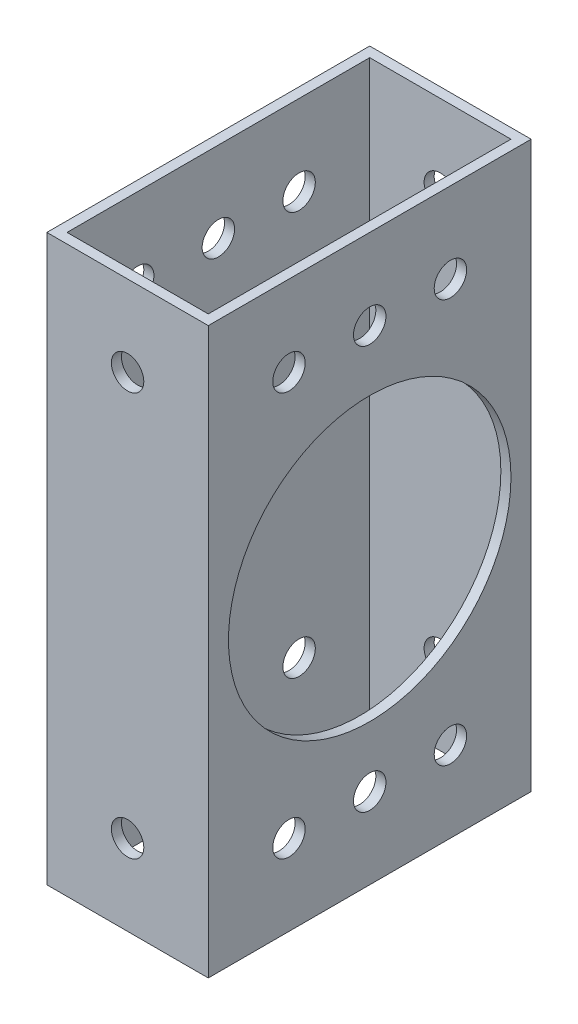
SolidWorks part; units mm, degrees
material "6061-T6 (SS)"
ref_plane "Front" through (0, 0, 0) normal (0, 0, 1) x (1, 0, 0)
ref_plane "Top" through (0, 0, 0) normal (0, 1, 0) x (1, 0, 0)
ref_plane "Right" through (0, 0, 0) normal (1, 0, 0) x (0, 0, -1)
sketch "Sketch1" plane through (0, 0, 0) normal (0, 1, 0) x (1, 0, 0)
  line L1 (12.7, 25.4) -> (-12.7, 25.4)
  line L2 (12.7, 25.4) -> (12.7, -25.4)
  line L3 (12.7, -25.4) -> (-12.7, -25.4)
  line L4 (-12.7, 25.4) -> (-12.7, -25.4)
  line L5 (12.7, 25.4) -> (-12.7, -25.4) construction
  line L6 (12.7, -25.4) -> (-12.7, 25.4) construction
  point P0 (0, 0)
  dimension "D1" = 25.4
  dimension "D2" = 50.8
extrude "Extrude-Thin1" add sketch "Sketch1" along normal up to surface (88.9 mm away) thin thin type one direction reverse wall 1.5875
sketch "Sketch4" plane through (-12.7, 0, 0) normal (-1, 0, 0) x (0, 0, 1)
  line L0 (-12.7, 12.7) -> (12.7, 12.7) construction
  line L3 (-12.7, 76.2) -> (12.7, 76.2) construction
  line L5 (-25.4, 0) -> (25.4, 0) construction
  line L6 (-25.4, 88.9) -> (25.4, 88.9) construction
  point P0 (-12.7, 76.2)
  point P2 (0, 76.2)
  point P4 (12.7, 76.2)
  point P6 (-12.7, 12.7)
  point P8 (0, 12.7)
  point P10 (12.7, 12.7)
  dimension "D1" = 12.7
  dimension "D2" = 12.7
  dimension "D3" = 12.7
  dimension "D4" = 12.7
hole_wizard "#10 Clearance Hole1" positions "Sketch4" profile "Sketch3" hole size "#10" standard "ANSI Inch" end condition through all
sketch "Sketch3" plane through (-12.7, 76.2, -12.7) normal (0, 1, 0) x (0, 0, 1)
  line L0 (0, 0) -> (0, 25.4)
  line L1 (0, 25.4) -> (2.5527, 25.4)
  line L2 (2.5527, 25.4) -> (2.5527, 0)
  line L5 (2.5527, 0) -> (0, 0)
  line L11 (0, -6.35) -> (0, 107.95) construction
  dimension "Thru Hole Dia." = 5.1054
  dimension "Thru Hole Depth" = 25.4
sketch "Sketch7" plane through (0, 0, 25.4) normal (0, 0, 1) x (1, 0, 0)
  line L0 (-12.7, 0) -> (12.7, 0) construction
  line L1 (-12.7, 88.9) -> (12.7, 88.9) construction
  point P0 (0, 12.7)
  point P2 (0, 76.2)
  dimension "D1" = 12.7
  dimension "D2" = 12.7
hole_wizard "#10 Clearance Hole2" positions "Sketch7" profile "Sketch6" hole size "#10" standard "ANSI Inch" end condition through all
sketch "Sketch6" plane through (0, 12.7, 25.4) normal (1, 0, 0) x (0, -1, 0)
  line L0 (0, 0) -> (0, 50.8)
  line L1 (0, 50.8) -> (2.5527, 50.8)
  line L2 (2.5527, 50.8) -> (2.5527, 0)
  line L5 (2.5527, 0) -> (0, 0)
  line L11 (0, -6.35) -> (0, 107.95) construction
  dimension "Thru Hole Dia." = 5.1054
  dimension "Thru Hole Depth" = 50.8
sketch "Sketch8" plane through (-12.7, 0, 0) normal (-1, 0, 0) x (0, 0, 1)
  line L0 (-25.4, 0) -> (25.4, 88.9) construction
  line L1 (25.4, 88.9) -> (25.4, 0) construction
  line L2 (-25.4, 88.9) -> (25.4, 88.9) construction
  line L3 (-25.4, 88.9) -> (-25.4, 0) construction
  line L4 (-25.4, 0) -> (25.4, 0) construction
  line L5 (10.8183, 46.99) -> (13.0175, 46.99)
  line L7 (13.0175, 41.91) -> (10.8183, 41.91)
  arc A0 (10.8183, 46.99) -> (10.8183, 41.91) centre (0, 44.45) ccw
  arc A1 (13.0175, 46.99) -> (13.0175, 41.91) centre (13.0175, 44.45) cw
  dimension "D1" = 22.225
  dimension "D2" = 4.445
  dimension "D3" = 5.08
extrude "Cut-Extrude1" cut sketch "Sketch8" against normal through all
sketch "Sketch9" plane through (12.7, 0, 0) normal (1, 0, 0) x (0, 0, -1)
  circle A0 centre (0, 44.45) radius 22.225
  circle A1 centre (0, 44.45) radius 11.1125 construction
  dimension "D1" = 44.45
extrude "Cut-Extrude2" cut sketch "Sketch9" against normal up to next
